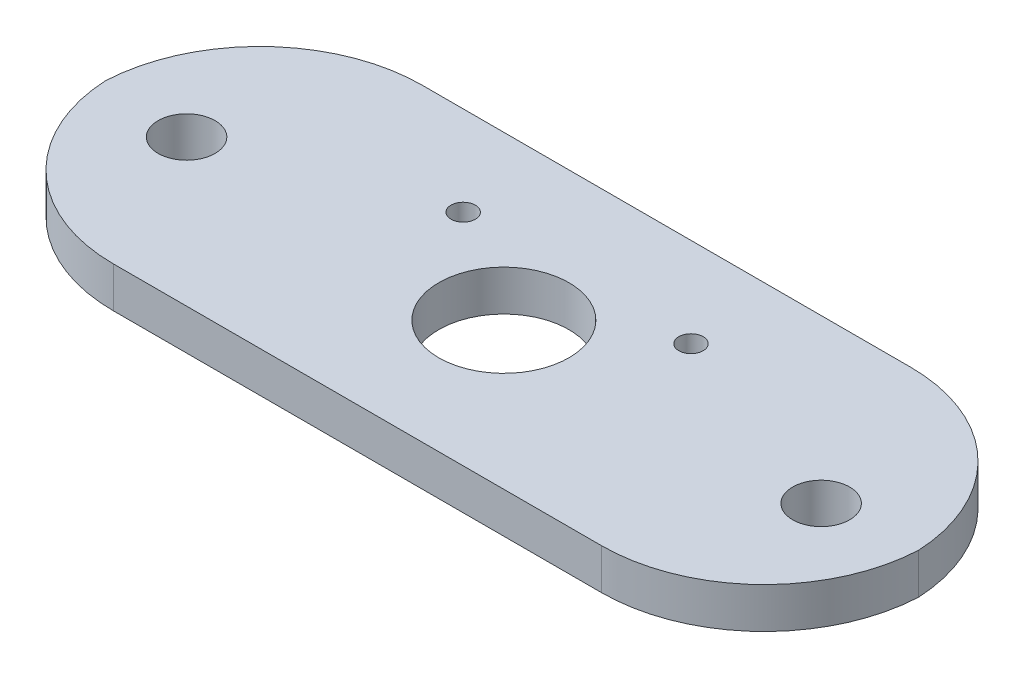
SolidWorks part; units mm, degrees
ref_plane "前视基准面" through (0, 0, 0) normal (0, 0, 1) x (1, 0, 0)
ref_plane "上视基准面" through (0, 0, 0) normal (0, 1, 0) x (1, 0, 0)
ref_plane "右视基准面" through (0, 0, 0) normal (1, 0, 0) x (0, 0, -1)
sketch "草图1" plane through (0, 0, 0) normal (0, 1, 0) x (1, 0, 0)
  line L1 (-50, 20) -> (50, 20)
  line L2 (-50, 20) -> (-50, -18)
  line L3 (-50, -18) -> (50, -18)
  line L4 (50, 20) -> (50, -18)
  line L5 (0, -18) -> (0, 20) construction
  line L6 (-50, 0) -> (50, 0) construction
  circle A0 centre (0, 0) radius 8
  circle A1 centre (39, 0) radius 3.5
  circle A2 centre (-39, 0) radius 3.5
  point P0 (0, 0)
  dimension "D3" = 16
  dimension "D4" = 7
  dimension "D1" = 38
  dimension "D2" = 100
  dimension "D5" = 78
  dimension "D6" = 20
extrude "凸台-拉伸1" add sketch "草图1" along normal blind 5
fillet "圆角1" radius 20 4 edges at (-50, 2.5, -20) (-50, 2.5, 18) (50, 2.5, -20) (50, 2.5, 18)
hole_wizard "大小mm Transitional 暗销孔1" positions "草图2" profile "草图3" hole size "Ø3.0" standard "GB" end condition through all
sketch "草图2" plane through (0, 5, 0) normal (0, 1, 0) x (1, 0, 0)
  line L0 (0, -4.1879) -> (0, 16.2588) construction
  line L2 (16.4412, 0) -> (-18.8394, 0) construction
  point P0 (14, 9)
  point P3 (-14, 9)
  point P20 (0, 0)
  dimension "D1" = 9
  dimension "D2" = 14
sketch "草图3" plane through (14, 5, -9) normal (1, 0, 0) x (0, 0, 1)
  line L0 (0, 0) -> (0, 5)
  line L1 (0, 5) -> (1.5, 5)
  line L2 (1.5, 5) -> (1.5, 0)
  line L5 (1.5, 0) -> (0, 0)
  line L11 (0, -6.35) -> (0, 107.95) construction
  dimension "通孔孔直径" = 3
  dimension "通孔孔深度" = 5
